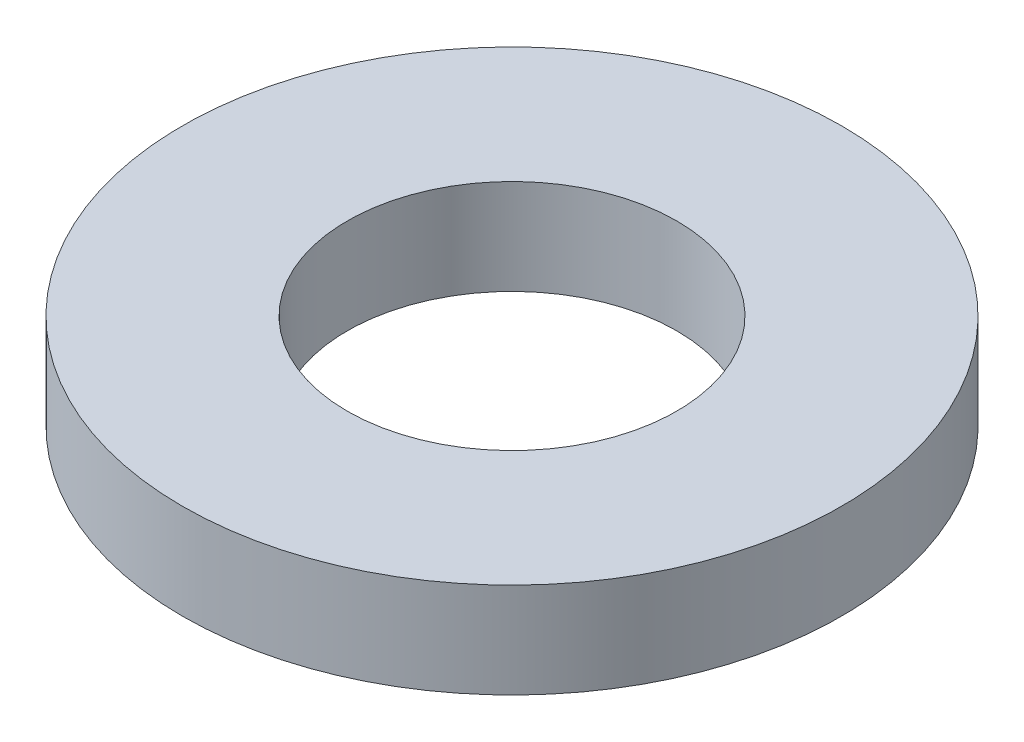
SolidWorks part; units mm, degrees
ref_plane "Front Plane" through (0, 0, 0) normal (0, 0, 1) x (1, 0, 0)
ref_plane "Top Plane" through (0, 0, 0) normal (0, 1, 0) x (1, 0, 0)
ref_plane "Right Plane" through (0, 0, 0) normal (1, 0, 0) x (0, 0, -1)
sketch "Sketch1" plane through (0, 0, 0) normal (0, 1, 0) x (1, 0, 0)
  circle A0 centre (0, 0) radius 90
  dimension "FLANGE_OD" = 180
extrude "Boss-Extrude1" add sketch "Sketch1" along normal blind 26
sketch "Sketch2" plane through (0, 0, 0) normal (0, 1, 0) x (1, 0, 0)
  circle A0 centre (0, 0) radius 45
  dimension "BORE_D" = 90
extrude "Cut-Extrude1" cut sketch "Sketch2" along normal through all
sketch "Sketch3" plane through (0, 26, 0) normal (0, 1, 0) x (1, 0, 0)
  circle A0 centre (0, 0) radius 27.4924 construction
  circle A1 centre (-27.4924, 0) radius 6.3435
  dimension "BOLT_D" = 12.6869
  dimension "BOLT_PCD" = 54.9848
extrude "Cut-Extrude2" cut sketch "Sketch3" against normal blind 24.0999 rebuild error yes
pattern_circular "CirPattern1" count 8 over 360 rebuild error yes
